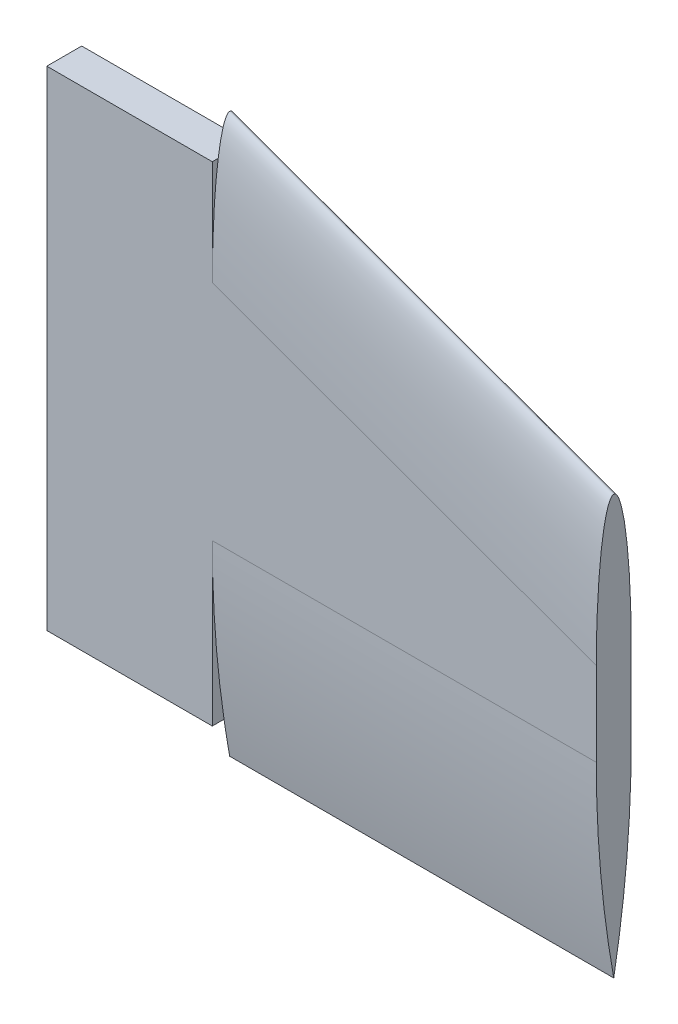
SolidWorks part; units mm, degrees
other "Markup1"
sketch "Sketch2" plane through (0, -5, 5) normal (-0.9994, -0.0223, 0.0275) x (0.021, 0.2509, 0.9678)
ref_plane "Front Plane" through (0, 0, 0) normal (0, 0, 1) x (1, 0, 0)
ref_plane "Top Plane" through (0, 0, 0) normal (0, 1, 0) x (1, 0, 0)
ref_plane "Right Plane" through (0, 0, 0) normal (1, 0, 0) x (0, 0, -1)
sketch "Sketch1" plane through (0, 0, 0) normal (0, 0, 1) x (1, 0, 0)
  line L0 (0, 0) -> (0, 70)
  line L1 (0, 70) -> (23.7, 70)
  line L5 (78.7, -5) -> (23.7, -5)
  line L6 (23.7, -5) -> (23.7, 0)
  line L7 (23.7, 0) -> (0, 0)
  line L8 (23.7, 70) -> (23.7, 75)
  line L9 (23.7, 75) -> (78.7, 55)
  line L10 (78.7, 55) -> (78.7, -5)
  line L11 (23.7, 75) -> (23.7, -5) construction
  point P3 (23.7, 35)
  point P10 (0, 35)
  dimension "D1" = 80
  dimension "D2" = 60
  dimension "D3" = 55
  dimension "D4" = 23.7
  dimension "D5" = 70
extrude "Boss-Extrude1" add sketch "Sketch1" along normal blind 5
sketch "Sketch4" plane through (78.7, 0, 0) normal (1, 0, 0) x (0, 0, -1)
  line L0 (-5, 55) -> (0, 55) construction
  line L1 (-5, 35) -> (0, 35) construction
  line L2 (-5, -5) -> (-5, 55) construction
  line L3 (0, -5) -> (0, 55) construction
  line L4 (-5, 35) -> (-5, 55)
  line L5 (-5, 55) -> (0, 55)
  line L6 (0, 55) -> (0, 35)
  ellipse E0 centre (-2.5, 35) end of major axis (-2.5, 55) minor radius 2.5 (0, 35) -> (-5, 35) ccw
  line M3 (0, -5) -> (0, 55)
  line M4 (0, 55) -> (-5, 55)
  line M5 (-5, 55) -> (-5, -5)
  dimension "D1" = 20
extrude "Cut-Extrude2" cut sketch "Sketch4" along direction (-0.9398, 0.3417, 0) on the side against the normal up to surface (55 mm away) contours E0 L5 M5 | E0 M3 M4
sketch "Sketch5" plane through (78.7, 0, 0) normal (1, 0, 0) x (0, 0, -1)
  line L0 (-5, -5) -> (0, -5) construction
  line L1 (0, -5) -> (0, 35) construction
  line L2 (-158.05, 23) -> (0, 23) construction
  line L3 (-2.5, -5) -> (-2.5, 55) construction
  line L4 (-5, 23) -> (-5, -5)
  line L5 (-5, -5) -> (0, -5)
  line L6 (0, -5) -> (0, 23)
  circle A0 centre (-158.05, 23) radius 158.05 construction
  arc A1 (0, 23) -> (-2.5, -5) centre (-158.05, 23) cw
  arc A2 (-5, 23) -> (-2.5, -5) centre (153.05, 23) ccw
  ellipse E0 centre (-2.5, 35) end of major axis (-2.5, 55) minor radius 2.5 (0, 35) -> (-5, 35) ccw construction
  point P0 (-2.5, -5)
  line M4 (0, -5) -> (0, 35)
  line M6 (-5, 35) -> (-5, -5)
  line M7 (-5, -5) -> (0, -5)
  dimension "D2" = 316.1
  dimension "D1" = 28
extrude "Cut-Extrude3" cut sketch "Sketch5" against normal up to surface (55 mm away) contours A2 M6 M7 | A1 L5 M4 up to face at (23.7, -2.5, 2.5)
